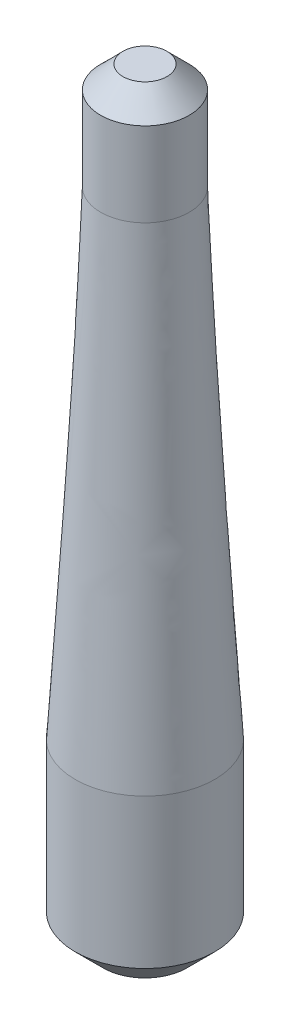
SolidWorks part; units mm, degrees
ref_plane "Front Plane" through (0, 0, 0) normal (0, 0, 1) x (1, 0, 0)
ref_plane "Top Plane" through (0, 0, 0) normal (0, 1, 0) x (1, 0, 0)
ref_plane "Right Plane" through (0, 0, 0) normal (1, 0, 0) x (0, 0, -1)
sketch "Sketch1" plane through (0, 0, 0) normal (0, 1, 0) x (1, 0, 0)
  circle A0 centre (0, 0) radius 2.5
  dimension "D1" = 5
ref_plane "Plane1" through (0, 17.145, 0) normal (0, 1, 0) x (1, 0, 0)
sketch "Sketch2" plane through (0, 17.145, 0) normal (0, 1, 0) x (1, 0, 0)
  circle A0 centre (0, 0) radius 1.5875
  dimension "D1" = 3.175
loft "Loft1" add profiles "Sketch2", "Sketch1" connector at (-0.3774, 17.145, 1.542) connector at (-1.6918, 0, 1.8406)
sketch "Sketch3" plane through (0, 0, 0) normal (0, -1, 0) x (1, 0, 0)
  circle A1 centre (0, 0) radius 2.5
  circle A2 centre (0, 0) radius 2.5
  dimension "D1" = 0
extrude "Boss-Extrude1" add sketch "Sketch3" along normal blind 6.35
sketch "Sketch4" plane through (0, 17.145, 0) normal (0, 1, 0) x (1, 0, 0)
  circle A1 centre (0, 0) radius 1.5875
  circle A2 centre (0, 0) radius 1.5875
  dimension "D1" = 0
extrude "Boss-Extrude2" add sketch "Sketch4" along normal blind 3.81
chamfer "Chamfer5" distance 1 1 edges at (0, -6.35, -2.5)
chamfer "Chamfer6" distance 0.8 angle 45 1 edges at (0, 20.955, 1.5875)
